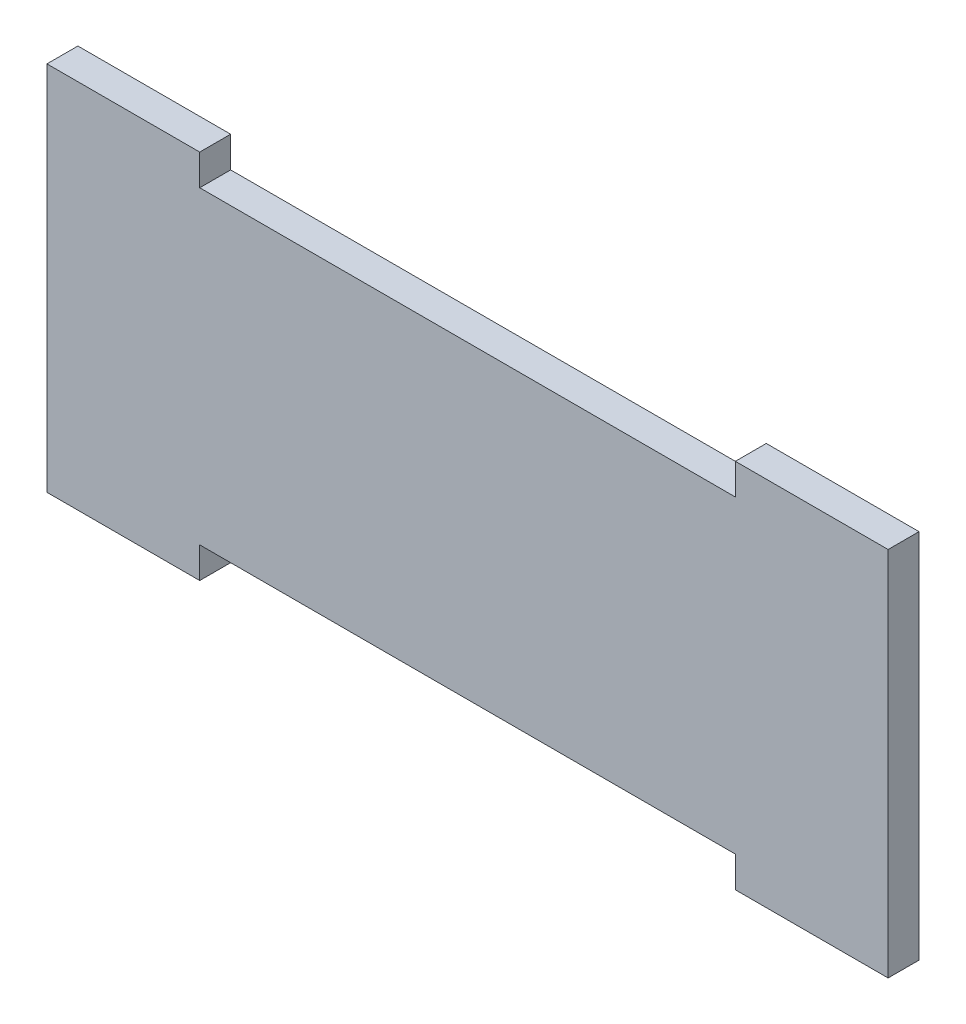
SolidWorks part; units mm, degrees
ref_plane "Front Plane" through (0, 0, 0) normal (0, 0, 1) x (1, 0, 0)
ref_plane "Top Plane" through (0, 0, 0) normal (0, 1, 0) x (1, 0, 0)
ref_plane "Right Plane" through (0, 0, 0) normal (1, 0, 0) x (0, 0, -1)
sketch "Sketch1" plane through (0, 0, 0) normal (0, 0, 1) x (1, 0, 0)
  line L1 (-68, 50) -> (68, 50)
  line L2 (-68, 50) -> (-68, 0)
  line L3 (-68, 0) -> (68, 0)
  line L4 (68, 50) -> (68, 0)
  point P4 (0, 0)
  dimension "D1" = 136
  dimension "D2" = 50
extrude "Boss-Extrude1" add sketch "Sketch1" along normal blind 5
sketch "Sketch2" plane through (0, 50, 0) normal (0, 1, 0) x (1, 0, 0)
  line L0 (68, -5) -> (-68, -5) construction
  line L1 (-68, 0) -> (-43.3, 0)
  line L2 (-68, 0) -> (-68, -5)
  line L3 (-68, -5) -> (-43.3, -5)
  line L4 (-43.3, 0) -> (-43.3, -5)
  line L6 (68, 0) -> (43.3, 0)
  line L7 (68, 0) -> (68, -5)
  line L8 (68, -5) -> (43.3, -5)
  line L9 (43.3, 0) -> (43.3, -5)
  dimension "D1" = 24.7
  dimension "D2" = 24.7
extrude "Boss-Extrude2" add sketch "Sketch2" along normal blind 5
sketch "Sketch3" plane through (0, 0, 0) normal (0, -1, 0) x (1, 0, 0)
  line L0 (-68, 0) -> (68, 0) construction
  line L1 (-68, 5) -> (-43.3, 5)
  line L2 (-68, 5) -> (-68, 0)
  line L3 (-68, 0) -> (-43.3, 0)
  line L4 (-43.3, 5) -> (-43.3, 0)
  line L6 (68, 5) -> (43.3, 5)
  line L7 (68, 5) -> (68, 0)
  line L8 (68, 0) -> (43.3, 0)
  line L9 (43.3, 5) -> (43.3, 0)
  dimension "D1" = 24.7
  dimension "D2" = 24.7
extrude "Boss-Extrude3" add sketch "Sketch3" along normal blind 5
